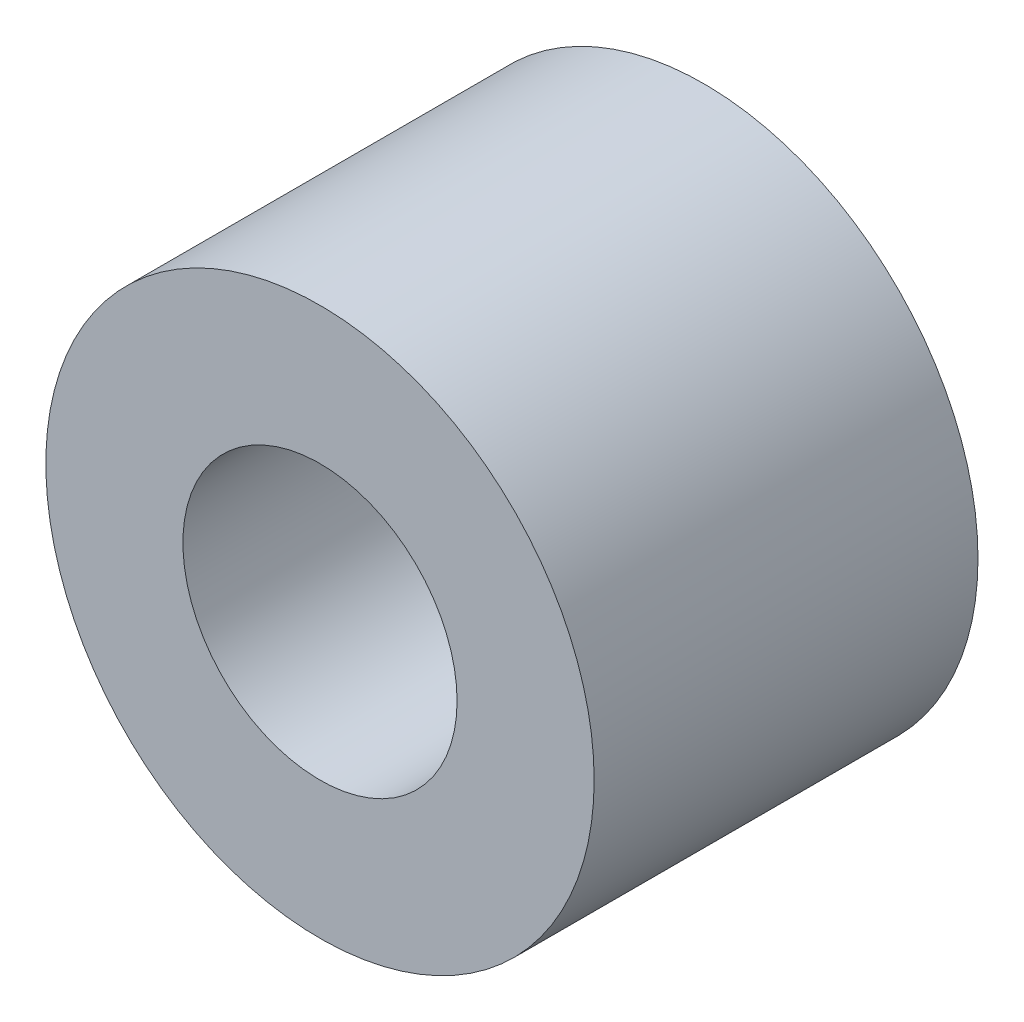
SolidWorks part; units mm, degrees
ref_plane "Alzado" through (0, 0, 0) normal (0, 0, 1) x (1, 0, 0)
ref_plane "Planta" through (0, 0, 0) normal (0, 1, 0) x (1, 0, 0)
ref_plane "Vista lateral" through (0, 0, 0) normal (1, 0, 0) x (0, 0, -1)
sketch "Croquis1" plane through (0, 0, 0) normal (0, 0, 1) x (1, 0, 0)
  circle A2 centre (45.5, 14.8) radius 2.5
  circle A3 centre (45.5, 14.8) radius 5
  dimension "D1" = 10
  dimension "D2" = 5
extrude "Saliente-Extruir1" add sketch "Croquis1" along normal blind 7
